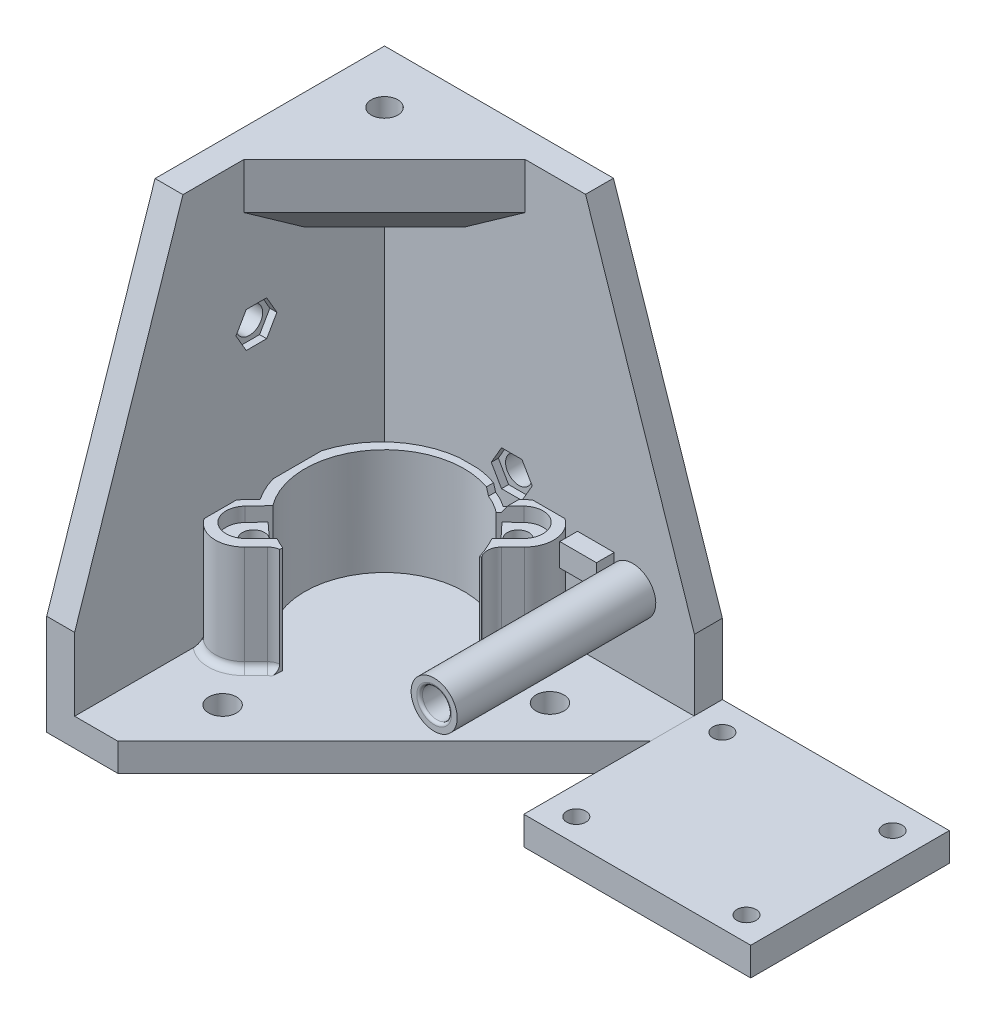
SolidWorks part; units mm, degrees
ref_plane "Front" through (0, 0, 0) normal (0, 0, 1) x (1, 0, 0)
ref_plane "Top" through (0, 0, 0) normal (0, 1, 0) x (1, 0, 0)
ref_plane "Right" through (0, 0, 0) normal (1, 0, 0) x (0, 0, -1)
sketch "Sketch1" plane through (0, 0, 0) normal (0, 1, 0) x (1, 0, 0)
  line L0 (0, 0) -> (0, 60.5)
  line L1 (0, -55) -> (0, 55) construction
  line L2 (0, 60.5) -> (60.5, 60.5)
  line L3 (60.5, 60.5) -> (60.5, 47.75)
  line L4 (60.5, 47.75) -> (12.75, 0)
  line L5 (-55, 0) -> (55, 0) construction
  line L6 (12.75, 0) -> (0, 0)
  dimension "D1" = 60.5
  dimension "D2" = 12.75
extrude "Boss-Extrude1" add sketch "Sketch1" along normal blind 5
sketch "Sketch4" plane through (0, 0, 0) normal (-1, 0, 0) x (0, 0, 1)
  line L0 (-60.5, 5) -> (-60.5, 76.1962)
  line L1 (-60.5, 76.1962) -> (-19.4, 76.1962)
  line L2 (-19.4, 76.1962) -> (0, 18.0048)
  line L3 (0, 18.0048) -> (0, 5)
  line L4 (0, -37.675) -> (0, 37.675) construction
  line L5 (-60.5, 5) -> (0, 5) construction
  line L6 (-60.5, 5) -> (0, 5)
  dimension "D1" = 71.1962
  dimension "D2" = 41.1
  dimension "D3" = 61.34
extrude "Boss-Extrude2" add sketch "Sketch4" against normal blind 5
sketch "Sketch5" plane through (0, 0, -60.5) normal (0, 0, -1) x (-1, 0, 0)
  line L0 (0, 76.1962) -> (-41, 76.1962)
  line L1 (-41, 76.1962) -> (-60.5, 17.7009)
  line L2 (-60.5, 17.7009) -> (-60.5, 5)
  line L6 (-60.5, 0) -> (0, 0)
  line L7 (0, 0) -> (0, 76.1962)
  line L8 (0, 76.1962) -> (-5, 76.1962)
  line L9 (-5, 76.1962) -> (-5, 5)
  line L10 (-5, 5) -> (-60.5, 5)
  line L11 (-60.5, 5) -> (-60.5, 0)
  line L12 (-60.5, 0) -> (0, 0)
  line L13 (0, 0) -> (0, 76.1962)
  line L14 (0, 76.1962) -> (-5, 76.1962)
  line L15 (-5, 76.1962) -> (-5, 5)
  line L16 (-5, 5) -> (-60.5, 5)
  line L17 (-60.5, 5) -> (-60.5, 0)
  line M13 (-5, 76.1962) -> (-5, 5)
  line M14 (-5, 5) -> (-60.5, 5)
  dimension "D2" = 41
  dimension "D3" = 61.66
  dimension "D1" = 0
extrude "Boss-Extrude3" add sketch "Sketch5" against normal blind 5 contours L1 L2 L0 M14 M13 region at (29.1655, 37.8824, -60.5)
sketch "Sketch6" plane through (0, 5, 0) normal (0, 1, 0) x (1, 0, 0)
  line L0 (60.5, 60.5) -> (0, 60.5) construction
  line L4 (0, 19.4) -> (0, 0)
  line L5 (60.5, 55.5) -> (5, 55.5)
  line L6 (5, 55.5) -> (5, 0)
  line L7 (5, 0) -> (12.75, 0)
  line L8 (12.75, 0) -> (60.5, 47.75)
  line L9 (60.5, 47.75) -> (60.5, 55.5)
  line L10 (60.5, 55.5) -> (5, 55.5)
  line L11 (5, 55.5) -> (5, 0)
  line L12 (5, 0) -> (12.75, 0)
  line L13 (12.75, 0) -> (60.5, 47.75)
  line L14 (60.5, 47.75) -> (60.5, 55.5)
  line L15 (0, 0) -> (5, 0)
  line L16 (5, 0) -> (5, 19.4)
  line L17 (5, 19.4) -> (0, 19.4)
  line L18 (0, 19.4) -> (0, 0)
  line L19 (0, 0) -> (5, 0)
  line L20 (5, 0) -> (5, 19.4)
  line L21 (5, 19.4) -> (0, 19.4)
  line L24 (0, 60.5) -> (0, 19.4)
  line L25 (0, 19.4) -> (5, 19.4)
  line L26 (5, 19.4) -> (5, 55.5)
  line L27 (5, 55.5) -> (41, 55.5)
  line L28 (41, 55.5) -> (41, 60.5)
  line L29 (41, 60.5) -> (0, 60.5)
  line L30 (0, 60.5) -> (0, 19.4)
  line L31 (0, 19.4) -> (5, 19.4)
  line L32 (5, 19.4) -> (5, 55.5)
  line L33 (5, 55.5) -> (41, 55.5)
  line L34 (41, 55.5) -> (41, 60.5)
  line L35 (41, 60.5) -> (0, 60.5)
  circle A0 centre (16.5, 15) radius 2.5
  circle A1 centre (45.5, 44.625) radius 2.5
  dimension "D1" = 5
  dimension "D2" = 5
  dimension "D3" = 0
  dimension "D4" = 15
  dimension "D6" = 16.5
  dimension "D7" = 15
  dimension "D9" = 15.875
  dimension "D5" = 0
  dimension "D8" = 0
extrude "Cut-Extrude1" cut sketch "Sketch6" against normal through all contours A0 | A1 region at (16.5, 5, -15) region at (45.5, 5, -44.625)
sketch "Sketch9" plane through (0, 0, -55.5) normal (0, 0, 1) x (1, 0, 0)
  line L1 (5, 76.1962) -> (5, 5) construction
  line L5 (0, 0) -> (60.5, 0)
  line L6 (0, 76.1962) -> (0, 0)
  line L7 (41, 76.1962) -> (0, 76.1962)
  line L8 (60.5, 17.7009) -> (41, 76.1962)
  line L9 (60.5, 0) -> (60.5, 17.7009)
  line L10 (0, 0) -> (60.5, 0)
  line L11 (0, 76.1962) -> (0, 0)
  line L12 (41, 76.1962) -> (0, 76.1962)
  line L13 (60.5, 17.7009) -> (41, 76.1962)
  line L14 (60.5, 0) -> (60.5, 17.7009)
  line L15 (49.45, 19.0462) -> (49.45, 3.6199) construction
  circle A0 centre (49.45, 19.0462) radius 4.1275
  circle A1 centre (49.45, 19.0462) radius 2.6035
  dimension "D2" = 5.207
  dimension "D3" = 1.524
  dimension "D4" = 57.15
  dimension "D5" = 44.45
  dimension "D1" = 0
extrude "Boss-Extrude5" add sketch "Sketch9" along normal blind 35.56 contours A1 A0 region at (45.4392, 19.0462, -55.5)
fillet "Fillet1" radius 0.508 1 edges at (52.0535, 19.0462, -19.94)
sketch "Sketch14" plane through (0, 5, 0) normal (0, 1, 0) x (1, 0, 0)
  line L0 (13.4627, 27.5396) -> (14.7681, 26.7924)
  line L1 (12.75, 0) -> (60.5, 47.75) construction
  line L2 (36.625, 23.875) -> (5, 55.5) construction
  line L3 (5, 55.5) -> (60.5, 55.5) construction
  line L4 (32.9604, 47.0373) -> (33.7076, 45.7319)
  line L5 (14.8281, 26.8523) -> (11.8274, 23.8516)
  line L6 (6.723, 28.8027) -> (9.1327, 31.3641)
  line L7 (33.6477, 45.6719) -> (36.6484, 48.6726)
  line L8 (31.6973, 53.777) -> (29.1359, 51.3673)
  line L9 (15.0744, 24.4582) -> (13.006, 22.3898)
  line L10 (5.6561, 29.7396) -> (7.0609, 31.1444)
  line L11 (36.0418, 45.4256) -> (38.1102, 47.494)
  line L12 (30.7604, 54.8439) -> (28.83, 52.9135)
  line L13 (18.1324, 24.8665) -> (30.5234, 17.7734)
  line L14 (35.6335, 42.3676) -> (42.7266, 29.9766)
  line L15 (31.7409, 18.9909) -> (18.852, 25.7543)
  line L16 (41.5091, 28.7591) -> (34.7457, 41.648)
  line L17 (16.5689, 25.6946) -> (16.5343, 25.1798)
  line L18 (34.7457, 41.648) -> (35.7996, 42.0774)
  circle A0 centre (20.5607, 39.9393) radius 14.2875
  arc A1 (11.8274, 23.8516) -> (6.723, 28.8027) centre (9.3129, 26.3661) cw
  arc A2 (36.6484, 48.6726) -> (31.6973, 53.777) centre (34.1339, 51.1871) ccw
  arc A3 (13.006, 22.3898) -> (5.6561, 29.7396) centre (9.3311, 26.0647) cw
  arc A4 (38.1102, 47.494) -> (30.7604, 54.8439) centre (34.4353, 51.1689) ccw
  arc A5 (7.0609, 31.1444) -> (28.83, 52.9135) centre (20.0709, 39.9035) cw
  arc A6 (36.0418, 45.4256) -> (35.6335, 42.3676) centre (37.8378, 43.6295) ccw
  arc A7 (15.0744, 24.4582) -> (18.1324, 24.8665) centre (16.8705, 22.6622) cw
  arc A9 (33.8602, 45.8844) -> (36.3595, 38.5726) centre (13.6025, 34.877) cw
  arc A10 (14.6156, 26.6398) -> (21.9274, 24.1405) centre (25.623, 46.8975) ccw
  point P40 (34.6689, 44.0527)
  point P43 (16.4473, 25.8311)
  line M13 (60.5, 55.5) -> (5, 55.5)
  line M14 (5, 55.5) -> (5, 0)
  line M16 (12.75, 0) -> (60.5, 47.75)
  dimension "D1" = 28.575
  dimension "D2" = 3.556
  dimension "D3" = 2.54
extrude "Boss-Extrude6" add sketch "Sketch14" along normal blind 19.05 contours L2 A0 L5 A1 L6 A5 L10 A3 L9 A7 L13 M16 M14 | L2 L14 A6 L11 A4 L12 A5 A0 L8 A2 L7 M16 M13 region at (7.691, 5, -30.3062) region at (10.0875, 5, -50.8829)
sketch "Sketch15" plane through (0, 76.1962, 0) normal (0, 1, 0) x (1, 0, 0)
  line L0 (5, 30.3375) -> (30.1625, 55.5)
  line L1 (0, -33.275) -> (0, 33.275) construction
  line L2 (41, 60.5) -> (0, 60.5) construction
  line L6 (0, 60.5) -> (0, 19.4)
  line L7 (0, 19.4) -> (5, 19.4)
  line L8 (5, 19.4) -> (5, 55.5)
  line L9 (5, 55.5) -> (41, 55.5)
  line L10 (41, 55.5) -> (41, 60.5)
  line L11 (41, 60.5) -> (0, 60.5)
  line L13 (0, 19.4) -> (5, 19.4)
  line L14 (5, 30.3375) -> (5, 55.5)
  line L15 (5, 55.5) -> (30.1625, 55.5)
  line L16 (41, 55.5) -> (41, 60.5)
  circle A0 centre (9.525, 50.975) radius 2.3812
  line M11 (5, 19.4) -> (5, 55.5)
  line M12 (5, 55.5) -> (41, 55.5)
  dimension "D3" = 4.7625
  dimension "D4" = 9.525
  dimension "D5" = 9.525
  dimension "D2" = 45
  dimension "D1" = 0
extrude "Boss-Extrude7" add sketch "Sketch15" against normal blind 15.875 contours L0 A0 M11 M12 region at (13.6178, 76.1962, -46.8822)
chamfer "Chamfer2" distance 7.62 angle 45 1 edges at (17.5813, 60.3212, -42.9187)
fillet "Fillet2" radius 1.27 7 edges at (39.6065, 5, -51.6871) (37.076, 5, -46.4598) (35.3202, 5, -43.9657) (8.8129, 5, -20.8935) (14.0402, 5, -23.424) (15.745, 5, -24.9392) (35.7165, 5, -42.2225)
sketch "Sketch16" plane through (0, 0, -55.5) normal (0, 0, 1) x (1, 0, 0)
  line L1 (46.1305, 23.2107) -> (38.2864, 23.2107)
  line L2 (46.1305, 23.2107) -> (46.1305, 19.0978)
  line L3 (46.1305, 19.0978) -> (38.2864, 19.0978)
  line L4 (38.2864, 23.2107) -> (38.2864, 19.0978)
extrude "Boss-Extrude8" add sketch "Sketch16" along normal blind 3.175
chamfer "Chamfer3" distance 1.27 angle 45 1 edges at (38.2864, 23.2107, -55.0794)
sketch "Sketch17" plane through (0, 5, 0) normal (0, 1, 0) x (1, 0, 0)
  line L0 (8.716, 30.9212) -> (14.047, 26.0712)
  line L1 (36.625, 23.875) -> (5, 55.5) construction
  line L2 (12.75, 0) -> (60.5, 47.75) construction
  line L3 (5, 55.5) -> (18.418, 55.5) construction
  line L4 (5, 55.5) -> (5, 44.2452) construction
  line L5 (29.6632, 51.8634) -> (34.5959, 46.6202)
  line L22 (37.3079, 55.5) -> (31.5627, 55.5)
  line L23 (30.7604, 54.8439) -> (28.83, 52.9135)
  line L24 (21.7238, 55.5) -> (18.418, 55.5)
  line L25 (5, 44.2452) -> (5, 35.5618)
  line L26 (7.0609, 31.1444) -> (5.6561, 29.7396)
  line L27 (5, 28.9373) -> (5, 23.1921)
  line L28 (13.006, 22.3898) -> (15.0744, 24.4582)
  line L29 (16.5343, 25.1798) -> (16.5689, 25.6946)
  line L30 (16.5343, 25.1798) -> (16.5689, 25.6946)
  line L31 (35.539, 41.9712) -> (35.7996, 42.0774)
  line L32 (35.539, 41.9712) -> (35.7996, 42.0774)
  line L33 (14.6156, 26.6398) -> (11.8274, 23.8516)
  line L34 (6.723, 28.8027) -> (9.1327, 31.3641)
  line L35 (29.1359, 51.3673) -> (31.6973, 53.777)
  line L36 (36.6484, 48.6726) -> (33.8602, 45.8844)
  line L40 (35.7996, 42.0774) -> (35.6335, 42.3676)
  line L41 (36.0418, 45.4256) -> (38.1102, 47.494)
  line L43 (37.3079, 55.5) -> (31.5627, 55.5)
  line L44 (30.7604, 54.8439) -> (28.83, 52.9135)
  line L45 (21.7238, 55.5) -> (18.418, 55.5)
  line L46 (5, 44.2452) -> (5, 35.5618)
  line L47 (7.0609, 31.1444) -> (5.6561, 29.7396)
  line L48 (5, 28.9373) -> (5, 23.1921)
  line L49 (13.006, 22.3898) -> (15.0744, 24.4582)
  line L54 (14.6156, 26.6398) -> (11.8274, 23.8516)
  line L55 (6.723, 28.8027) -> (9.1327, 31.3641)
  line L56 (29.1359, 51.3673) -> (31.6973, 53.777)
  line L57 (36.6484, 48.6726) -> (33.8602, 45.8844)
  line L61 (35.7996, 42.0774) -> (35.6335, 42.3676)
  line L62 (36.0418, 45.4256) -> (38.1102, 47.494)
  circle A1 centre (33.6908, 50.7324) radius 2.1828
  circle A2 centre (10.0204, 27.0078) radius 1.9844
  circle A3 centre (33.6908, 50.7324) radius 1.9288
  arc A15 (38.1102, 47.494) -> (37.3079, 55.5) centre (34.4353, 51.1689) ccw
  arc A17 (31.5627, 55.5) -> (30.7604, 54.8439) centre (34.4353, 51.1689) ccw
  arc A18 (28.83, 52.9135) -> (21.7238, 55.5) centre (20.0709, 39.9035) ccw
  arc A19 (18.418, 55.5) -> (5, 44.2452) centre (20.0709, 39.9035) ccw
  arc A20 (5, 35.5618) -> (7.0609, 31.1444) centre (20.0709, 39.9035) ccw
  arc A21 (5.6561, 29.7396) -> (5, 28.9373) centre (9.3311, 26.0647) ccw
  arc A22 (5, 23.1921) -> (13.006, 22.3898) centre (9.3311, 26.0647) ccw
  arc A23 (16.5343, 25.1798) -> (15.0744, 24.4582) centre (16.8705, 22.6622) ccw
  arc A24 (14.6156, 26.6398) -> (16.5689, 25.6946) centre (25.623, 46.8975) ccw
  arc A25 (6.723, 28.8027) -> (11.8274, 23.8516) centre (9.3129, 26.3661) ccw
  arc A26 (29.1359, 51.3673) -> (9.1327, 31.3641) centre (20.5607, 39.9393) ccw
  arc A27 (36.6484, 48.6726) -> (31.6973, 53.777) centre (34.1339, 51.1871) ccw
  arc A28 (35.539, 41.9712) -> (33.8602, 45.8844) centre (13.6025, 34.877) ccw
  arc A29 (36.0418, 45.4256) -> (35.6335, 42.3676) centre (37.8378, 43.6295) ccw
  arc A30 (38.1102, 47.494) -> (37.3079, 55.5) centre (34.4353, 51.1689) ccw
  arc A32 (31.5627, 55.5) -> (30.7604, 54.8439) centre (34.4353, 51.1689) ccw
  arc A33 (28.83, 52.9135) -> (21.7238, 55.5) centre (20.0709, 39.9035) ccw
  arc A34 (18.418, 55.5) -> (5, 44.2452) centre (20.0709, 39.9035) ccw
  arc A35 (5, 35.5618) -> (7.0609, 31.1444) centre (20.0709, 39.9035) ccw
  arc A36 (5.6561, 29.7396) -> (5, 28.9373) centre (9.3311, 26.0647) ccw
  arc A37 (5, 23.1921) -> (13.006, 22.3898) centre (9.3311, 26.0647) ccw
  arc A38 (16.5343, 25.1798) -> (15.0744, 24.4582) centre (16.8705, 22.6622) ccw
  arc A39 (14.6156, 26.6398) -> (16.5689, 25.6946) centre (25.623, 46.8975) ccw
  arc A40 (6.723, 28.8027) -> (11.8274, 23.8516) centre (9.3129, 26.3661) ccw
  arc A41 (29.1359, 51.3673) -> (9.1327, 31.3641) centre (20.5607, 39.9393) ccw
  arc A42 (36.6484, 48.6726) -> (31.6973, 53.777) centre (34.1339, 51.1871) ccw
  arc A43 (35.539, 41.9712) -> (33.8602, 45.8844) centre (13.6025, 34.877) ccw
  arc A44 (36.0418, 45.4256) -> (35.6335, 42.3676) centre (37.8378, 43.6295) ccw
  line M44 (33.8602, 45.8844) -> (36.6484, 48.6726)
  arc M45 (36.6484, 48.6726) -> (31.6973, 53.777) centre (34.1339, 51.1871) ccw
  line M46 (31.6973, 53.777) -> (29.1359, 51.3673)
  line M48 (9.1327, 31.3641) -> (6.723, 28.8027)
  arc M49 (6.723, 28.8027) -> (11.8274, 23.8516) centre (9.3129, 26.3661) ccw
  line M50 (11.8274, 23.8516) -> (14.6156, 26.6398)
  dimension "D2" = 3.9688
  dimension "D3" = 0.254
  dimension "D1" = 0
extrude "Boss-Extrude9" add sketch "Sketch17" along normal offset from surface (16.51 mm away) 2.54 contours L5 A1 M46 M44 M45 | L0 M48 M49 M50 | A1 L5 A3 region at (11.3737, 5, -28.4876) region at (30.7585, 5, -52.737) region at (33.0584, 5, -52.7569) up to face at (20.9693, 24.05, -39.9839)
sketch "Sketch18" plane through (0, 0, 0) normal (-1, 0, 0) x (0, 0, 1)
  line L0 (-60.5, 76.1962) -> (-60.5, 0) construction
  line L1 (33.275, 0) -> (-33.275, 0) construction
  circle A0 centre (-32.56, 49.53) radius 2.3813
  dimension "D1" = 27.94
  dimension "D2" = 49.53
  dimension "D3" = 4.7625
extrude "Cut-Extrude2" cut sketch "Sketch18" against normal up to next
sketch "Sketch19" plane through (0, 0, -60.5) normal (0, 0, -1) x (-1, 0, 0)
  line L0 (0, 33.275) -> (0, -33.275) construction
  line L1 (33.275, 0) -> (-33.275, 0) construction
  circle A0 centre (-27.7812, 26.1937) radius 2.3813
  dimension "D1" = 27.7812
  dimension "D2" = 26.1937
  dimension "D3" = 4.7625
extrude "Cut-Extrude3" cut sketch "Sketch19" against normal up to next
sketch "Sketch20" plane through (0, 0, -55.5) normal (0, 0, 1) x (1, 0, 0)
  line L1 (31.4474, 26.1937) -> (29.6143, 29.3687)
  line L2 (29.6143, 29.3687) -> (25.9482, 29.3687)
  line L3 (25.9482, 29.3687) -> (24.1151, 26.1937)
  line L4 (24.1151, 26.1937) -> (25.9482, 23.0187)
  line L5 (25.9482, 23.0187) -> (29.6143, 23.0187)
  line L6 (29.6143, 23.0187) -> (31.4474, 26.1937)
  circle A0 centre (27.7812, 26.1937) radius 2.3813 construction
  circle A1 centre (27.7812, 26.1937) radius 2.3813
  circle A2 centre (27.7812, 26.1937) radius 3.175 construction
  dimension "D1" = 6.35
extrude "Cut-Extrude4" cut sketch "Sketch20" against normal blind 1.27 and the other way up to vertex (4.1327 mm away) contours L1 L2 L3 L4 L5 L6 other way up to point (29.1359, 24.05, -51.3673)
sketch "Sketch21" plane through (5, 0, 0) normal (1, 0, 0) x (0, 0, -1)
  line L1 (34.3931, 52.705) -> (30.7269, 52.705)
  line L2 (30.7269, 52.705) -> (28.8938, 49.53)
  line L3 (28.8938, 49.53) -> (30.7269, 46.355)
  line L4 (30.7269, 46.355) -> (34.3931, 46.355)
  line L5 (34.3931, 46.355) -> (36.2262, 49.53)
  line L6 (36.2262, 49.53) -> (34.3931, 52.705)
  circle A0 centre (32.56, 49.53) radius 2.3813 construction
  circle A1 centre (32.56, 49.53) radius 2.3812
  circle A2 centre (32.56, 49.53) radius 3.175 construction
  dimension "D1" = 6.35
extrude "Cut-Extrude5" cut sketch "Sketch21" against normal blind 1.27 contours L1 L2 L3 L4 L5 L6
sketch "Sketch23" plane through (0, 0, 0) normal (0, 1, 0) x (1, 0, 0)
  line L1 (60.5, 60.5) -> (101.14, 60.5)
  line L2 (60.5, 60.5) -> (60.5, 24.94)
  line L3 (60.5, 24.94) -> (101.14, 24.94)
  line L4 (101.14, 60.5) -> (101.14, 24.94)
  dimension "D1" = 40.64
  dimension "D2" = 35.56
extrude "Boss-Extrude12" add sketch "Sketch23" along normal blind 5.08
sketch "Sketch24" plane through (0, 5.08, 0) normal (0, 1, 0) x (1, 0, 0)
  line L0 (101.14, 60.5) -> (60.5, 60.5) construction
  line L1 (60.5, 47.75) -> (60.5, 55.5) construction
  circle A0 centre (65.58, 55.42) radius 1.7145
  circle A1 centre (96.06, 55.42) radius 1.7145
  circle A2 centre (96.06, 29.258) radius 1.7145
  circle A3 centre (65.58, 29.258) radius 1.7145
  dimension "D1" = 3.429
  dimension "D2" = 26.162
  dimension "D3" = 30.48
  dimension "D4" = 5.08
  dimension "D5" = 5.08
extrude "Cut-Extrude6" cut sketch "Sketch24" against normal up to next
